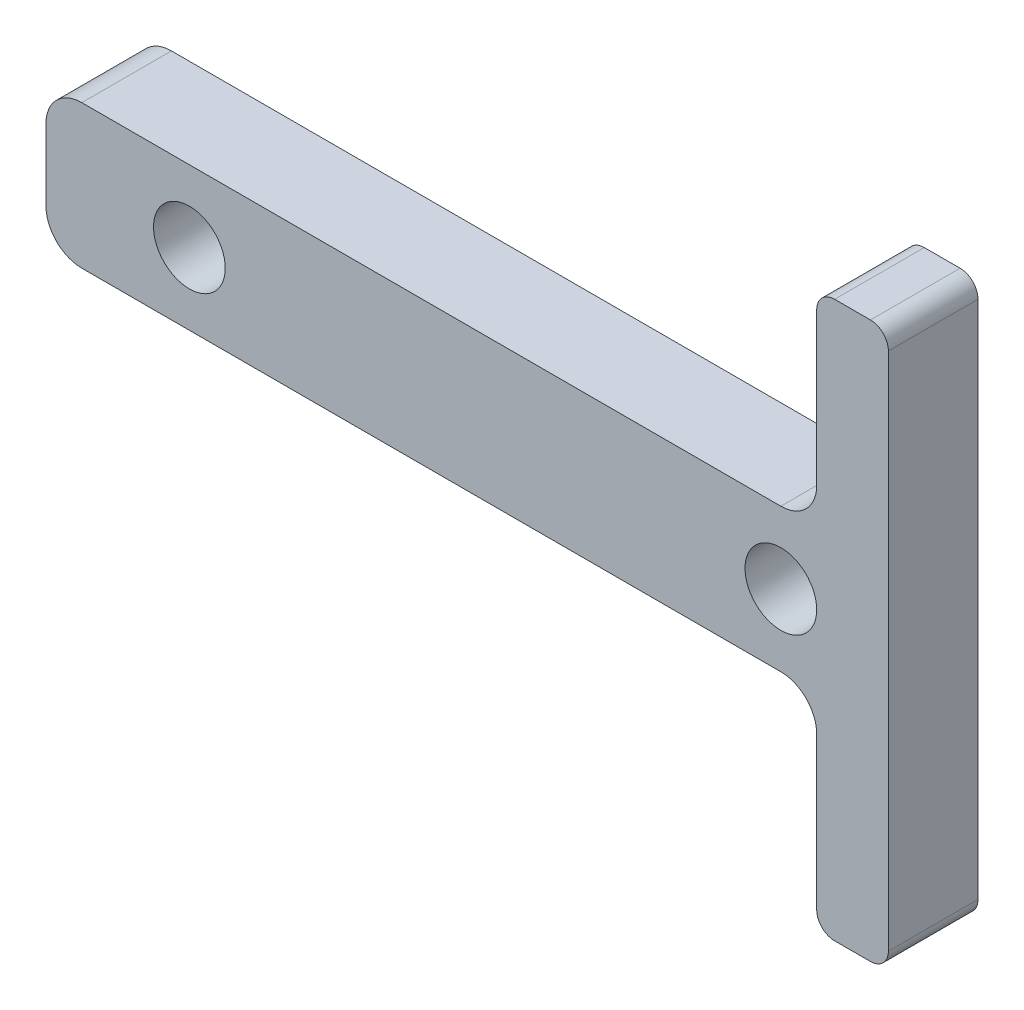
SolidWorks part; units mm, degrees
ref_plane "Front Plane" through (0, 0, 0) normal (0, 0, 1) x (1, 0, 0)
ref_plane "Top Plane" through (0, 0, 0) normal (0, 1, 0) x (1, 0, 0)
ref_plane "Right Plane" through (0, 0, 0) normal (1, 0, 0) x (0, 0, -1)
sketch "Sketch1" plane through (0, 0, 0) normal (0, 0, 1) x (1, 0, 0)
  line L0 (-19.5, 0) -> (19.5, 0)
  line L1 (-19.5, -8) -> (19.5, -8)
  line L2 (-21.5, -2) -> (-21.5, -6)
  line L3 (21.5, 2) -> (21.5, 10.5)
  line L4 (22.5, 11.5) -> (24.5, 11.5)
  line L5 (25.5, 10.5) -> (25.5, -18.5)
  line L6 (-21.5, -4) -> (35.202, -4) construction
  line L7 (21.5, -10) -> (21.5, -18.5)
  line L8 (22.5, -19.5) -> (24.5, -19.5)
  line L9 (-21.5, 0) -> (17.5, 0) construction
  line L10 (-21.5, -8) -> (17.5, -8) construction
  arc A0 (19.5, 0) -> (21.5, 2) centre (19.5, 2) ccw
  arc A1 (19.5, -8) -> (21.5, -10) centre (19.5, -10) cw
  arc A2 (-19.5, -8) -> (-21.5, -6) centre (-19.5, -6) cw
  arc A3 (-19.5, 0) -> (-21.5, -2) centre (-19.5, -2) ccw
  arc A4 (21.5, -18.5) -> (22.5, -19.5) centre (22.5, -18.5) ccw
  arc A5 (24.5, -19.5) -> (25.5, -18.5) centre (24.5, -18.5) ccw
  arc A6 (24.5, 11.5) -> (25.5, 10.5) centre (24.5, 10.5) cw
  arc A7 (21.5, 10.5) -> (22.5, 11.5) centre (22.5, 10.5) cw
  point P4 (0, 0)
  point P14 (25.5, -4)
  point P17 (21.5, 0)
  point P21 (21.5, -8)
  point P30 (21.5, -19.5)
  point P33 (25.5, -19.5)
  point P36 (25.5, 11.5)
  point P39 (21.5, 11.5)
  dimension "D5" = 2
  dimension "D1" = 1
  dimension "D3" = 4
  dimension "D4" = 31
  dimension "D6" = 43
  dimension "D2" = 8
extrude "Boss-Extrude1" add sketch "Sketch1" along normal blind 5
sketch "Sketch2" plane through (0, 0, 5) normal (0, 0, 1) x (1, 0, 0)
  line L0 (23.5, 11.5) -> (23.5, -21.4503) construction
  line L1 (24.5, 11.5) -> (22.5, 11.5) construction
  line L2 (-21.5, -4) -> (29.3804, -4) construction
  line L3 (-21.5, -2) -> (-21.5, -6) construction
  line L4 (21.5, 10.5) -> (21.5, 2) construction
  circle A1 centre (-13.5, -4) radius 2
  circle A2 centre (19.5, -4) radius 2
  dimension "D2" = 4
  dimension "D3" = 4
  dimension "D1" = 35
  dimension "D4" = 2
extrude "Cut-Extrude1" cut sketch "Sketch2" against normal through all
